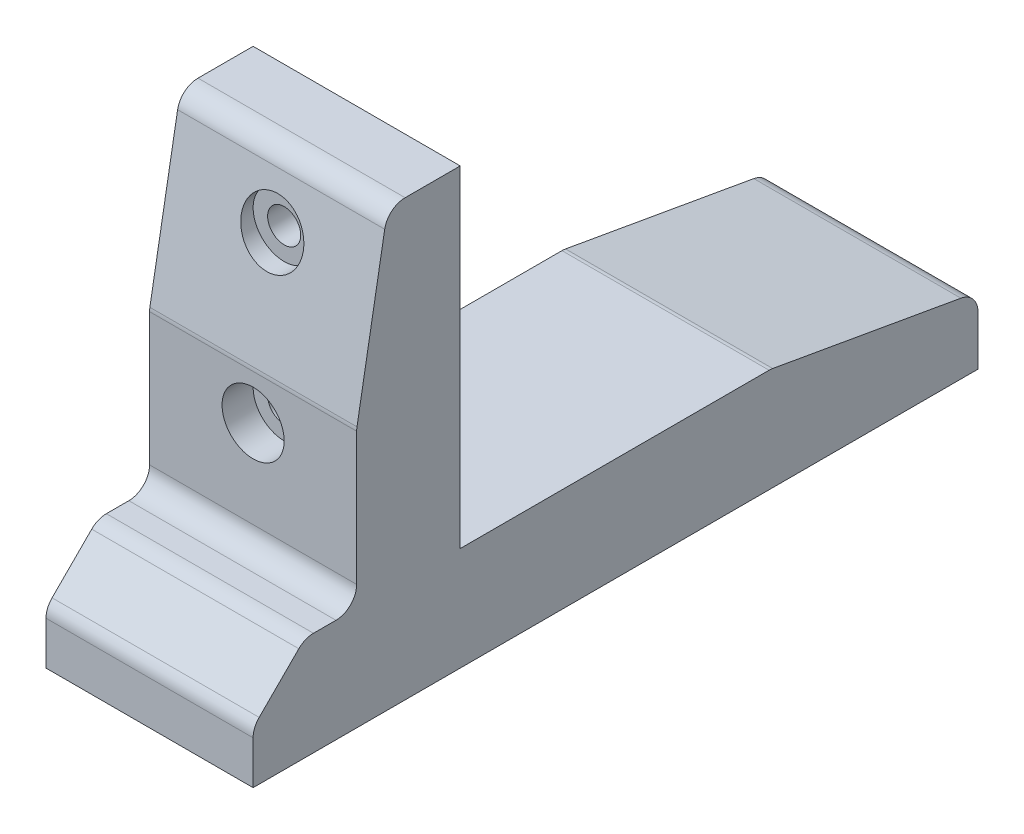
SolidWorks part; units mm, degrees
ref_plane "Front Plane" through (0, 0, 0) normal (0, 0, 1) x (1, 0, 0)
ref_plane "Top Plane" through (0, 0, 0) normal (0, 1, 0) x (1, 0, 0)
ref_plane "Right Plane" through (0, 0, 0) normal (1, 0, 0) x (0, 0, -1)
ref_plane "Plane1" through (37.1227, 0, 0) normal (1, 0, 0) x (0, 0, -1)
sketch "Sketch3" plane through (37.1227, 0, 0) normal (1, 0, 0) x (0, 0, -1)
  line L0 (0, -48.9607) -> (0, 81.0393) construction
  line L1 (0, -37.4607) -> (-10, -37.4607)
  line L2 (0, -37.4607) -> (0, -69.4607)
  line L3 (0, -69.4607) -> (-10, -69.4607)
  line L4 (-10, -37.4607) -> (-10, -69.4607)
  line L5 (19, -68.9607) -> (0, -68.9607) construction
  line L6 (-20, -79.4607) -> (50, -79.4607)
  line L7 (-20, -79.4607) -> (-20, -69.4607)
  line L8 (-20, -69.4607) -> (50, -69.4607)
  line L9 (50, -79.4607) -> (50, -69.4607)
  point P10 (19.0104, -51.4536)
  point P11 (0, -51.4536)
  dimension "D1" = 0.5
  dimension "D2" = 10
  dimension "D3" = 32
  dimension "D4" = 50
  dimension "D5" = 10
  dimension "D6" = 10
extrude "Boss-Extrude1" add sketch "Sketch3" along normal mid plane 20 contours L6 L9 L8 L3 L7 | L1 L4 L3 L2 region at (37.1227, -53.4607, 5) region at (37.1227, -74.4607, -15)
sketch "Sketch4" plane through (0, 0, 0) normal (0, 0, -1) x (-1, 0, 0)
  circle A0 centre (-37.1227, -58.9607) radius 1.6 construction
  circle A1 centre (-37.1227, -43.9607) radius 1.6 construction
  circle A2 centre (-37.1227, -58.9607) radius 1.6
  circle A3 centre (-37.1227, -43.9607) radius 1.6
  circle A4 centre (-37.1227, -43.9607) radius 3
  circle A5 centre (-37.1227, -58.9607) radius 3
  dimension "D1" = 6
extrude "Cut-Extrude1" cut sketch "Sketch4" against normal through all contours A3 | A2 region at (37.1227, -58.9607, 0) region at (37.1227, -43.9607, 0)
extrude "Cut-Extrude2" cut sketch "Sketch4<3>" along normal blind 3 from surface contours A4 A3 | A5 A2 region at (40.0378, -43.9607, 0) region at (40.0378, -58.9607, 0) starting at face at (37.1227, -42.3607, 10)
sketch "Sketch4<3>" plane through (0, 0, 0) normal (0, 0, -1) x (-1, 0, 0) same geometry as "Sketch4"
chamfer "Chamfer1" distance 20 angle 10 1 edges at (37.1227, -69.4607, -50) first distance on face at (37.1227, -69.4607, -25)
chamfer "Chamfer2" distance 5 angle 45 1 edges at (37.1227, -69.4607, 20)
chamfer "Chamfer3" distance 3 angle 80 1 edges at (37.1227, -37.4607, 10) first distance on face at (37.1227, -37.4607, 5)
fillet "Fillet1" radius 2 7 edges at (37.1227, -37.4607, 7) (37.1227, -54.4745, 10) (37.1227, -69.4607, 10) (37.1227, -69.4607, 15) (37.1227, -74.4607, 20) (37.1227, -69.4607, -30) (37.1227, -72.9872, -50)
